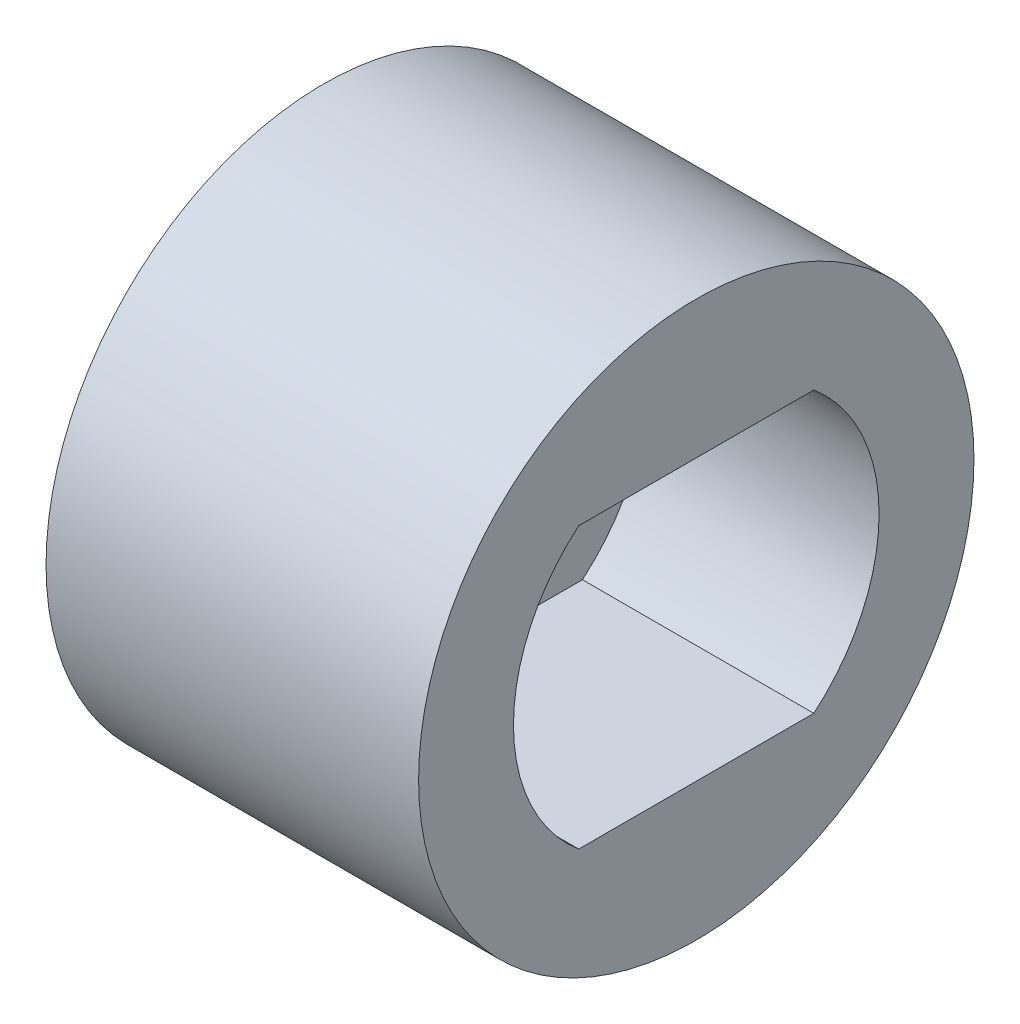
SolidWorks part; units mm, degrees
ref_plane "Plane1" through (0, 0, 0) normal (0, 0, 1) x (1, 0, 0)
ref_plane "Plane2" through (0, 0, 0) normal (0, 1, 0) x (1, 0, 0)
ref_plane "Plane3" through (0, 0, 0) normal (1, 0, 0) x (0, 0, -1)
other "Configuration Table"
sketch "HoldingSke" plane through (0, 0, 0) normal (0, 1, 0) x (1, 0, 0)
  line L0 (0, 0) -> (1.5094, -1.3121)
  line L1 (-15, 0) -> (100, 0) construction
  line L2 (0, 0) -> (-2.1039, 2.3779)
  line L3 (0, 0) -> (-11.863, 4.5341)
  line L4 (0, 0) -> (6.5177, 5.6657)
  line L5 (0, 0) -> (-23.7986, -8.8762)
  line L6 (0, 0) -> (-10.5278, -7.1032)
  line L7 (-2.1039, 2.3779) -> (3.3635, 27.1825)
  line L8 (-76.2, 2.8779) -> (-54.61, 2.8779)
  line L9 (-71.009, 38.7566) -> (-53.1078, 45.2721)
  line L10 (-76.2, 71.12) -> (104.1128, 71.12)
  line L11 (0, 0) -> (-5.1, 0)
  line L12 (-76.2, 101.6) -> (-76.181, 101.6)
  line L13 (24.9733, 27.94) -> (52.9518, 28.4284)
  line L14 (24.9733, 27.94) -> (24.9743, 27.94)
  line L15 (24.9733, 27.94) -> (100.4006, 29.5858)
  circle A0 centre (0, 0) radius 12
  circle A1 centre (0, 0) radius 12.7
  circle A2 centre (0, 0) radius 12.7
  dimension "Num_teeth" = 41
  dimension "Pitch_radius" = 180.3128
  dimension "Width" = 5.1
  dimension "Diameter" = 24
sketch "BasProSke" plane through (0, 0, 0) normal (0, 1, 0) x (1, 0, 0)
  line L0 (-10, 0) -> (60, 0) construction
  line L1 (0, 9.75) -> (0, 12)
  line L2 (0, 9.75) -> (5.1, 9.75)
  line L3 (5.1, 9.75) -> (5.1, 12)
  line L4 (5.1, 12) -> (0, 12)
  dimension "Thickness" = 5.1
  dimension "Diameter" = 24
revolve "Base-Revolve" add sketch "BasProSke" angle 360 about L0
sketch "TooCutSke" plane through (0, 0, 0) normal (1, 0, 0) x (0, 0, -1)
  line L3 (0.4401, 10.2405) -> (0.4401, 53.6633) construction
  line L4 (0, 0) -> (0, 59.563) construction
  line L5 (0, 0) -> (-5.2304, 68.127) construction
  line L6 (-4.3282, 8.3619) -> (37.0682, 11.5401) construction
  circle A0 centre (0, 0) radius 10.25 construction
  circle A1 centre (0, 0) radius 10.876 construction
  circle A2 centre (0, 0) radius 8.6687 construction
  circle A3 centre (0, 0) radius 9.7246 construction
  arc A4 (0.6177, 9.705) -> (0.1383, 10.8751) centre (-4.3282, 8.3619) ccw
  arc A5 (0.6177, 9.705) -> (-0.6177, 9.705) centre (0, 0) ccw
  arc A6 (0.1383, 10.8751) -> (-0.1383, 10.8751) centre (0, 0) ccw
  arc A7 (-0.1383, 10.8751) -> (-0.6177, 9.705) centre (4.3282, 8.3619) ccw
extrude "ToothCut" cut sketch "TooCutSke" along normal through all
fillet "Breaks" [suppressed] radius 0.05
fillet "RootFillets" [suppressed] radius 0.126
pattern_circular "TeethCuts" count 41 every 8.78 about axis through (-10, 0, 0) along (1, 0, 0) of "RootFillets", "Breaks", "ToothCut"
sketch "草图1" plane through (5.1, 0, 0) normal (1, 0, 0) x (0, 0, -1)
  line L1 (-7.9, -6.05) -> (7.9, -6.05)
  line L2 (-7.9, -6.05) -> (-7.9, 6.05)
  line L3 (-7.9, 6.05) -> (7.9, 6.05)
  line L4 (7.9, -6.05) -> (7.9, 6.05)
  line L5 (-7.9, -6.05) -> (7.9, 6.05) construction
  line L6 (-7.9, 6.05) -> (7.9, -6.05) construction
  circle A0 centre (0, 0) radius 2.5
  circle A1 centre (0, 0) radius 7.9
  circle A2 centre (0, 0) radius 12
  point P0 (0, 0)
  dimension "D3" = 5
  dimension "D4" = 24
  dimension "D1" = 15.8
  dimension "D2" = 12.1
extrude "凸台-拉伸1" add sketch "草图1" along normal blind 11 contours A2 A1 L3 L4 L1 L2 | A1 L3 L2 | L3 A1 | A1 L4 L3 | A1 L1 L4 | L1 A1 | A1 L2 L1 | L3 A1 L1 A0 region at (5.1, -4.5968, 7.0882) region at (5.1, -3.2534, 6.98) region at (5.1, -6.798, 0) region at (5.1, 4.5968, 7.0882) region at (5.1, -4.5968, -7.0882) region at (5.1, 6.798, 0) region at (5.1, 4.5968, -7.0882) region at (5.1, 0, 11.6606)
extrude "切除-拉伸1" cut sketch "草图1<3>" along normal up to next from offset 1 contours L3 A1 L1 A0 region at (5.1, -3.2534, 6.98)
sketch "草图1<3>" plane through (5.1, 0, 0) normal (1, 0, 0) x (0, 0, -1) same geometry as "草图1"
equation "' \"Module@HoldingSke\" = 6.35"
equation "' \"Num_teeth@HoldingSke\" = 24"
equation "' \"Ap@HoldingSke\" =  14.5"
equation "' \"Ap@HoldingSke\" = 14.5"
equation "' \"Width@HoldingSke\" = 12"
equation "' \"Diameter@HoldingSke\" = 8 * 25.4"
equation "' \"Show_teeth@HoldingSke\" = 100"
equation "' \"Backlash@HoldingSke\" = 0.009 * 25.4"
equation "' \"Addendum_fac@HoldingSke\" = 1.0"
equation "' \"Dedendum_fac@HoldingSke\" = 1.25"
equation "' \"Dedendum_add@HoldingSke\" = 0.00005 * 25.4"
equation "' \"Clearance_fac@HoldingSke\" = 0.25"
equation "\"Pitch@HoldingSke\" = 1 / \"Module@HoldingSke\" "
equation "\"Overcut_dia@TooCutSke\" = (\"Num_teeth@HoldingSke\" - 2 * \"Addendum_fac@HoldingSke\") / \"Pitch@HoldingSke\" - 0.002 * 25.4"
equation "\"Pitch_dia@TooCutSke\" = \"Num_teeth@HoldingSke\" / \"Pitch@HoldingSke\""
equation "\"Base_dia@TooCutSke\" = \"Num_teeth@HoldingSke\" / \"Pitch@HoldingSke\" * cos((\"Ap@HoldingSke\"  * 3.14159265 / 180)) * 0.90"
equation "\"Root_dia@TooCutSke\" = \"Num_teeth@HoldingSke\"  / \"Pitch@HoldingSke\" + 2 *  \"Dedendum_fac@HoldingSke\"/ \"Pitch@HoldingSke\" + \"Dedendum_add@HoldingSke\" * 2"
equation "\"Half_ang@TooCutSke\" = 180 / \"Num_teeth@HoldingSke\""
equation "\"Half_CT@TooCutSke\" = \"Num_teeth@HoldingSke\" / \"Pitch@HoldingSke\" * sin((3.14159265 / 2 / \"Num_teeth@HoldingSke\")) / 2 + 10 * \"Backlash@HoldingSke\" / 4"
equation "\"Flank_rad@TooCutSke\" = \"Num_teeth@HoldingSke\" / \"Pitch@HoldingSke\" / 4"
equation "\"Radius@RootFillets\"= \"Clearance_fac@HoldingSke\" / \"Pitch@HoldingSke\" + \"Dedendum_add@HoldingSke\""
equation "\"Break_rad@Breaks\" = 0.02 / \"Pitch@HoldingSke\" * 5"
equation "\"Num_teeth@TeethCuts\" = int( \"Show_teeth@HoldingSke\" ) + 1"
equation "\"Num_teeth@TeethCuts\" = ((sgn( \"Num_teeth@TeethCuts\" - \"Num_teeth@HoldingSke\" )-1)*( \"Num_teeth@TeethCuts\" - \"Num_teeth@HoldingSke\" ))/-2+ \"Num_teeth@HoldingSke\""
equation "\"Num_teeth@TeethCuts\" = ((sgn( \"Num_teeth@TeethCuts\" - 2.0)+1)*( \"Num_teeth@TeethCuts\" - 2.0))/2 +2.0"
equation "\"Angle@TeethCuts\" = 360.0 / \"Num_teeth@HoldingSke\""
equation "\"Diameter@BasProSke\" = \"Num_teeth@HoldingSke\"  / \"Pitch@HoldingSke\" + 2 *  \"Dedendum_fac@HoldingSke\"/ \"Pitch@HoldingSke\" + \"Dedendum_add@HoldingSke\" * 2 + 0.002 * 25.4"
equation "\"Diameter@BasProSke\" = ((sgn( \"Diameter@BasProSke\"  - \"Diameter@HoldingSke\" )+1)*( \"Diameter@BasProSke\"  - \"Diameter@HoldingSke\" ))/2 + \"Diameter@HoldingSke\""
equation "\"Inside_diameter@BasProSke\" =  (\"Num_teeth@HoldingSke\" - 2 * \"Addendum_fac@HoldingSke\") / \"Pitch@HoldingSke\" "
equation "\"Thickness@BasProSke\"  = \"Width@HoldingSke\""
